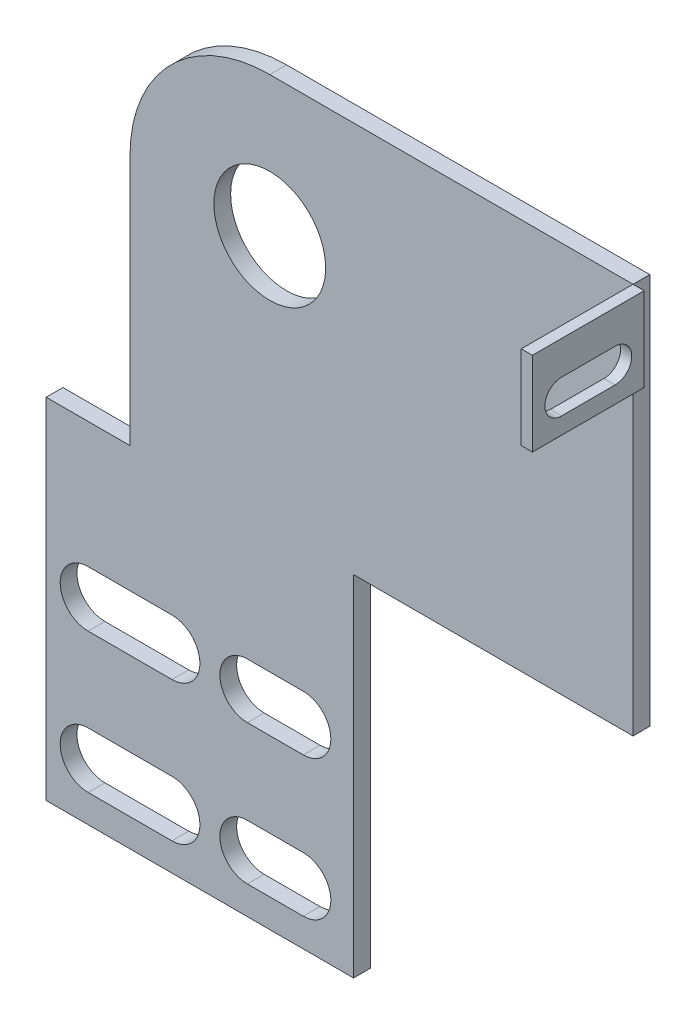
SolidWorks part; units mm, degrees
ref_plane "Front Plane" through (0, 0, 0) normal (0, 0, 1) x (1, 0, 0)
ref_plane "Top Plane" through (0, 0, 0) normal (0, 1, 0) x (1, 0, 0)
ref_plane "Right Plane" through (0, 0, 0) normal (1, 0, 0) x (0, 0, -1)
sketch "Sketch1" plane through (0, 0, 0) normal (0, 0, 1) x (1, 0, 0)
  line L1 (0, 0) -> (133.35, 0)
  line L2 (0, 0) -> (0, 168.275)
  line L3 (0, 168.275) -> (133.35, 168.275)
  line L4 (133.35, 0) -> (133.35, 168.275)
  dimension "D1" = 133.35
  dimension "D2" = 168.275
extrude "Boss-Extrude1" add sketch "Sketch1" along normal blind 3.81
sketch "Sketch2" plane through (0, 0, 0) normal (0, 0, 1) x (1, 0, 0)
  line L0 (0, 79.375) -> (19.05, 79.375)
  line L1 (0, 168.275) -> (0, 0) construction
  line L2 (19.05, 79.375) -> (19.05, 136.525)
  line L3 (133.35, 168.275) -> (0, 168.275) construction
  line L4 (50.8, 168.275) -> (133.35, 168.275)
  line L5 (133.35, 168.275) -> (133.35, 79.375)
  line L6 (133.35, 0) -> (133.35, 168.275) construction
  line L7 (133.35, 79.375) -> (69.85, 79.375)
  line L8 (69.85, 79.375) -> (69.85, 0)
  line L9 (0, 0) -> (133.35, 0) construction
  line L10 (69.85, 0) -> (0, 0)
  line L11 (0, 0) -> (0, 79.375)
  line L12 (9.525, 44.45) -> (28.575, 44.45) construction
  line L13 (9.525, 50.8) -> (28.575, 50.8)
  line L14 (9.525, 38.1) -> (28.575, 38.1)
  line L15 (9.525, 12.7) -> (28.575, 12.7) construction
  line L16 (9.525, 19.05) -> (28.575, 19.05)
  line L17 (9.525, 6.35) -> (28.575, 6.35)
  line L18 (45.72, 44.45) -> (58.42, 44.45) construction
  line L19 (45.72, 50.709) -> (58.42, 50.709)
  line L20 (45.72, 38.191) -> (58.42, 38.191)
  line L21 (45.72, 12.7) -> (58.42, 12.7) construction
  line L22 (45.72, 18.959) -> (58.42, 18.959)
  line L23 (45.72, 6.441) -> (58.42, 6.441)
  arc A0 (19.05, 136.525) -> (50.8, 168.275) centre (50.8, 136.525) cw
  circle A1 centre (50.8, 136.525) radius 12.7
  arc A2 (9.525, 50.8) -> (9.525, 38.1) centre (9.525, 44.45) ccw
  arc A3 (28.575, 38.1) -> (28.575, 50.8) centre (28.575, 44.45) ccw
  arc A4 (9.525, 19.05) -> (9.525, 6.35) centre (9.525, 12.7) ccw
  arc A5 (28.575, 6.35) -> (28.575, 19.05) centre (28.575, 12.7) ccw
  arc A6 (45.72, 50.709) -> (45.72, 38.191) centre (45.72, 44.45) ccw
  arc A7 (58.42, 38.191) -> (58.42, 50.709) centre (58.42, 44.45) ccw
  arc A8 (45.72, 18.959) -> (45.72, 6.441) centre (45.72, 12.7) ccw
  arc A9 (58.42, 6.441) -> (58.42, 18.959) centre (58.42, 12.7) ccw
  point P23 (19.05, 44.45)
  point P30 (19.05, 12.7)
  point P37 (52.07, 44.45)
  point P44 (52.07, 12.7)
  point P49 (0, 0)
  point P50 (7.0988, 6.441)
  point P51 (0, 0)
  point P52 (59.7206, 12.7)
  dimension "D4" = 25.4
  dimension "D5" = 31.75
  dimension "D6" = 6.35
  dimension "D12" = 6.259
  dimension "D1" = 19.05
  dimension "D2" = 63.5
  dimension "D3" = 88.9
  dimension "D7" = 19.05
  dimension "D8" = 12.7
  dimension "D9" = 19.05
  dimension "D10" = 12.7
  dimension "D11" = 44.45
  dimension "D13" = 45.72
extrude "Cut-Extrude1" cut sketch "Sketch2" along normal through all flip side to cut
ref_plane "Plane1" through (133.35, 0, 0) normal (1, 0, 0) x (0, 0, -1)
sketch "Sketch3" plane through (133.35, 0, 0) normal (1, 0, 0) x (0, 0, -1)
  line L0 (-22.5728, 156.845) -> (-10.4472, 156.845) construction
  line L1 (-3.81, 168.275) -> (-29.21, 168.275)
  line L2 (-3.81, 168.275) -> (-3.81, 149.225)
  line L3 (-3.81, 149.225) -> (-29.21, 149.225)
  line L4 (-29.21, 168.275) -> (-29.21, 149.225)
  line L5 (-22.5728, 160.655) -> (-10.4472, 160.655)
  line L6 (-22.5728, 153.035) -> (-10.4472, 153.035)
  arc A0 (-22.5728, 160.655) -> (-22.5728, 153.035) centre (-22.5728, 156.845) ccw
  arc A1 (-10.4472, 153.035) -> (-10.4472, 160.655) centre (-10.4472, 156.845) ccw
  point P7 (-16.51, 156.845)
  point P12 (-16.51, 168.275)
  dimension "D3" = 3.81
  dimension "D1" = 25.4
  dimension "D2" = 19.05
  dimension "D4" = 7.62
extrude "Boss-Extrude2" add sketch "Sketch3" along normal blind 2.54 separate body
